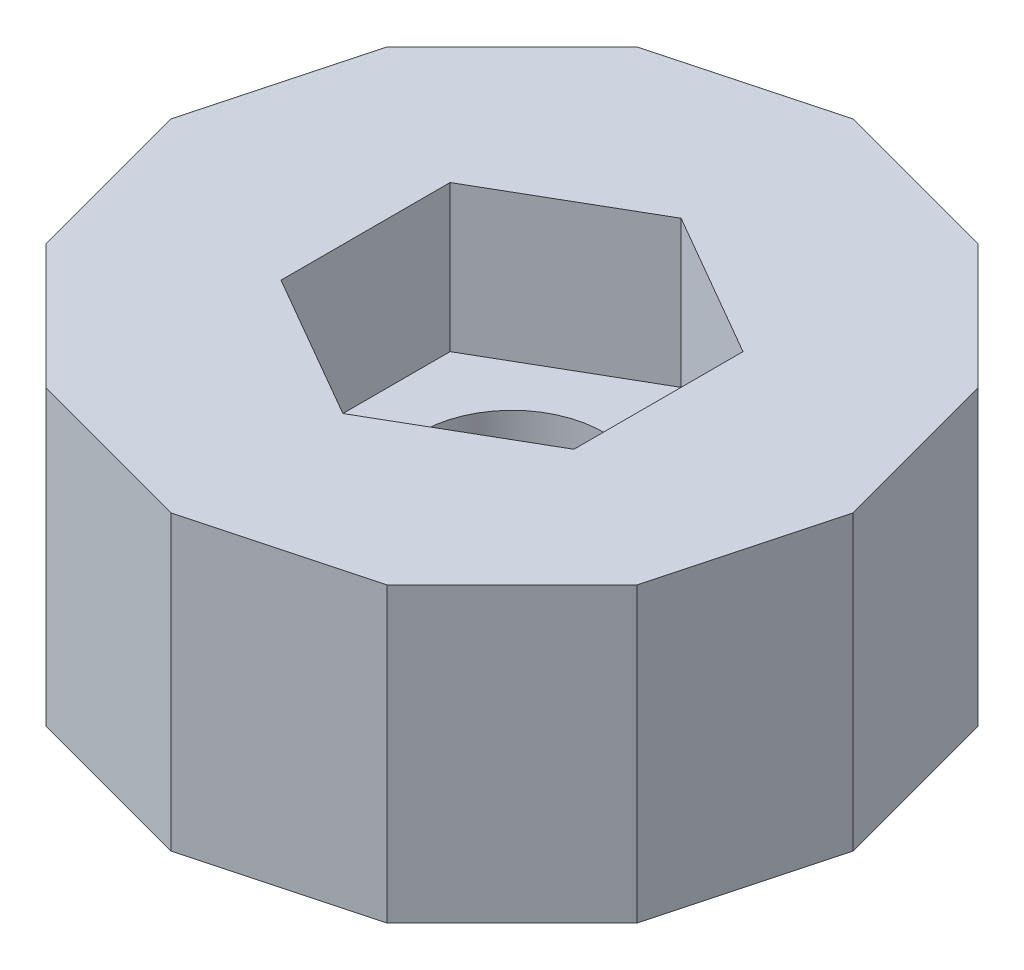
SolidWorks part; units mm, degrees
ref_plane "Plano frontal" through (0, 0, 0) normal (0, 0, 1) x (1, 0, 0)
ref_plane "Plano superior" through (0, 0, 0) normal (0, 1, 0) x (1, 0, 0)
ref_plane "Plano direito" through (0, 0, 0) normal (1, 0, 0) x (0, 0, -1)
sketch "Esboço1" plane through (0, 0, 0) normal (0, 1, 0) x (1, 0, 0)
  line L0 (0, 0) -> (0, 9.1014) construction
  line L1 (0, 0) -> (-11.8246, 0) construction
  line L3 (0, 4.6188) -> (-4, 2.3094)
  line L4 (-4, 2.3094) -> (-4, -2.3094)
  line L5 (-4, -2.3094) -> (0, -4.6188)
  line L6 (0, -4.6188) -> (4, -2.3094)
  line L7 (4, -2.3094) -> (4, 2.3094)
  line L8 (4, 2.3094) -> (0, 4.6188)
  line L9 (0, 9.3175) -> (-8.0692, 4.6587)
  line L10 (-8.0692, 4.6587) -> (-8.0692, -4.6587)
  line L11 (-8.0692, -4.6587) -> (0, -9.3175)
  line L12 (0, -9.3175) -> (8.0692, -4.6587)
  line L13 (8.0692, -4.6587) -> (8.0692, 4.6587)
  line L14 (8.0692, 4.6587) -> (0, 9.3175)
  line L15 (0, 9.3175) -> (-4.6587, 8.0692)
  line L16 (-4.6587, 8.0692) -> (-8.0692, 4.6587)
  line L17 (-8.0692, 4.6587) -> (-9.3175, 0)
  line L18 (-9.3175, 0) -> (-8.0692, -4.6587)
  line L19 (-8.0692, -4.6587) -> (-4.6587, -8.0692)
  line L20 (-4.6587, -8.0692) -> (0, -9.3175)
  line L21 (0, -9.3175) -> (4.6587, -8.0692)
  line L22 (4.6587, -8.0692) -> (8.0692, -4.6587)
  line L23 (8.0692, -4.6587) -> (9.3175, 0)
  line L24 (9.3175, 0) -> (8.0692, 4.6587)
  line L25 (8.0692, 4.6587) -> (4.6587, 8.0692)
  line L26 (4.6587, 8.0692) -> (0, 9.3175)
  circle A0 centre (0, 0) radius 2.5
  circle A1 centre (0, 0) radius 5
  circle A2 centre (0, 0) radius 4 construction
  circle A3 centre (0, 0) radius 8.0692 construction
  circle A4 centre (0, 0) radius 9 construction
  dimension "D1" = 5
  dimension "D2" = 10
  dimension "D3" = 18
extrude "Ressalto-extrusão1" add sketch "Esboço1" along normal blind 8 contours L13 L14 L9 L10 L11 L12 A1 | L15 L16 L9 | L25 L26 L14 | L23 L24 L13 | L21 L22 L12 | L19 L20 L11 | L17 L18 L10 | A1 L8 L7 L6 L5 L4 L3 region at (3.9113, 0, -6.7746) region at (4.2426, 0, -7.3485) region at (-4.2426, 0, -7.3485) region at (-8.4853, 0, 0) region at (8.4853, 0, 0) region at (-4.2426, 0, 7.3485) region at (4.2426, 0, 7.3485) region at (-4.8586, 0, 0)
extrude "Ressalto-extrusão2" add sketch "Esboço1<3>" along normal blind 4 contours L7 L8 L3 L4 L5 L6 A0 region at (1.9389, 0, -3.3583)
sketch "Esboço1<3>" plane through (0, 0, 0) normal (0, 1, 0) x (1, 0, 0) same geometry as "Esboço1"
